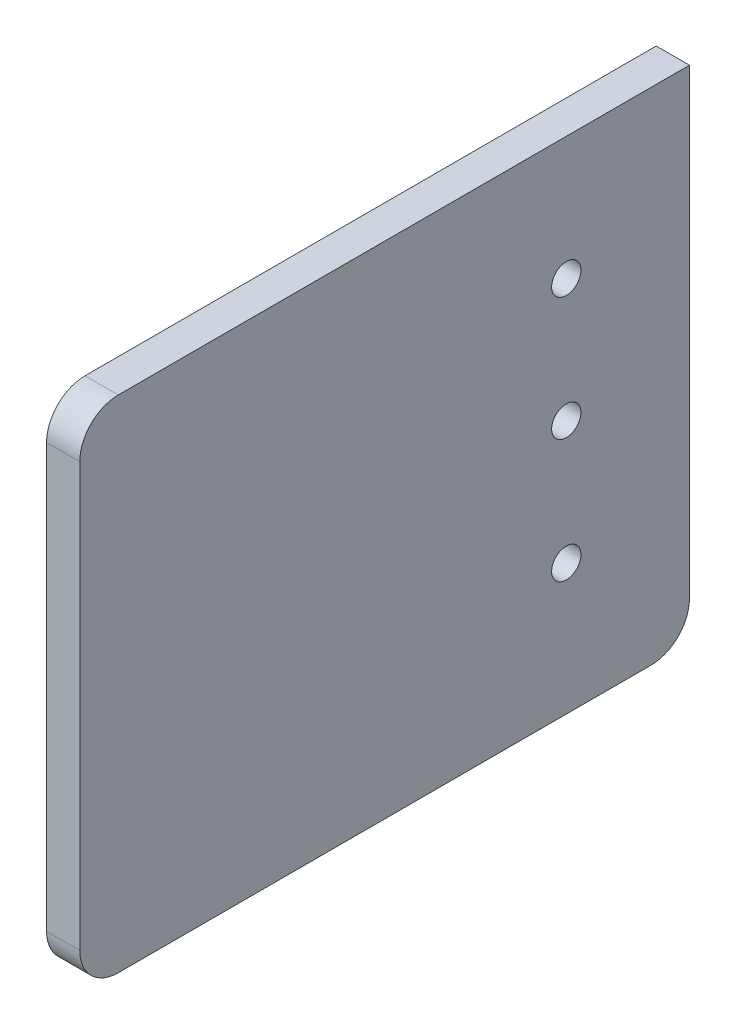
SolidWorks part; units mm, degrees
material "Acrylic (Medium-high impact)"
ref_plane "Front" through (0, 0, 0) normal (0, 0, 1) x (1, 0, 0)
ref_plane "Top" through (0, 0, 0) normal (0, 1, 0) x (1, 0, 0)
ref_plane "Right" through (0, 0, 0) normal (1, 0, 0) x (0, 0, -1)
ref_axis "side-side" through (80.9, 0, 0) along (-1, 0, 0)
ref_axis "up-down" through (0, 50, 0) along (0, -1, 0)
ref_axis "front-back" through (0, 0, -80.9) along (0, 0, 1)
sketch "Sketch2" plane through (0, 0, 0) normal (1, 0, 0) x (0, 0, -1)
  point P0 (79.196, 58)
sketch "Sketch1" plane through (0, 0, 0) normal (1, 0, 0) x (0, 0, -1)
  line L0 (84.5361, 65) -> (341.0178, 65) construction
  line L1 (0, 0) -> (79.196, 0)
  line L2 (0, 0) -> (0, 65)
  line L3 (0, 65) -> (79.196, 65)
  line L4 (79.196, 0) -> (79.196, 65)
  circle A0 centre (63.196, 49) radius 1.905
  circle A1 centre (63.196, 33) radius 1.905
  circle A2 centre (63.196, 17) radius 1.905
  dimension "D3" = 3.81
  dimension "D4" = 16
  dimension "D5" = 16
  dimension "D6" = 16
  dimension "D1" = 65
  dimension "D2" = 79.196
  dimension "D7" = 16
extrude "Boss-Extrude1" add sketch "Sketch1" along normal blind 4.318
fillet "Fillet1" radius 5 3 edges at (2.159, 65, 0) (2.159, 0, 0) (2.159, 0, -79.196)
